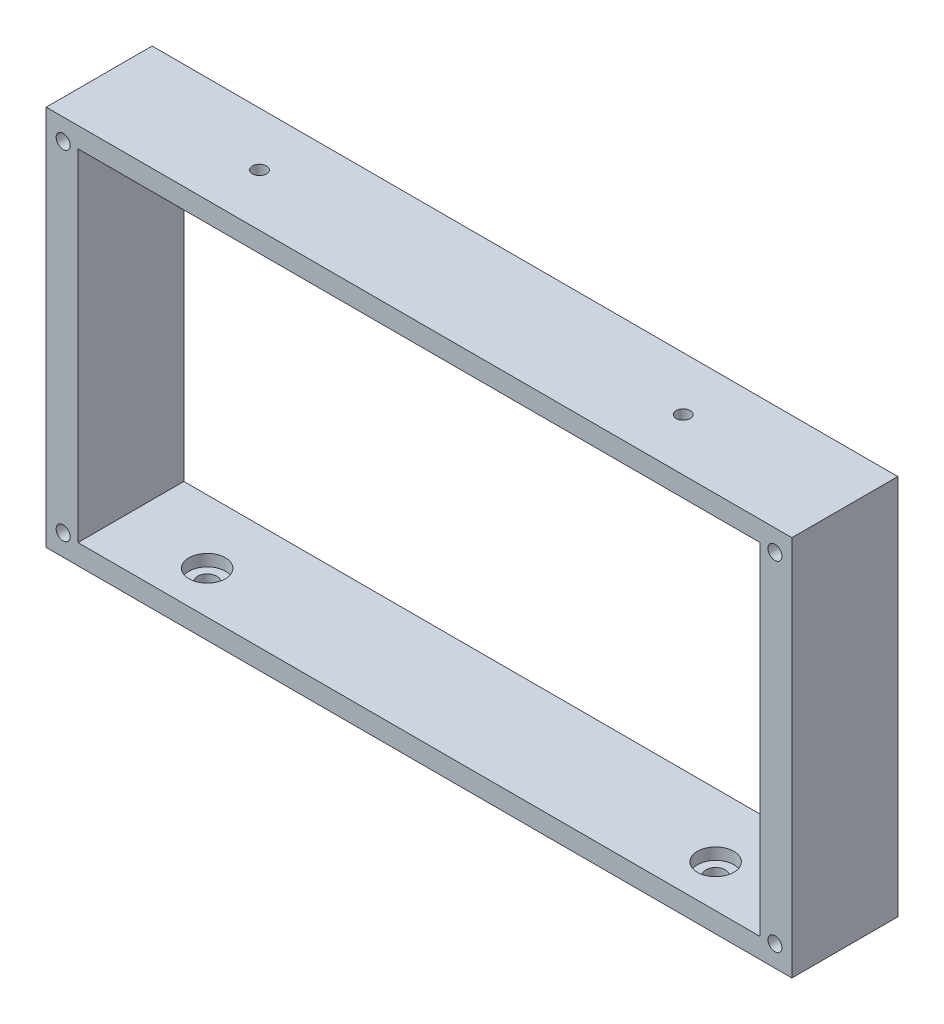
SolidWorks part; units mm, degrees
ref_plane "Front Plane" through (0, 0, 0) normal (0, 0, 1) x (1, 0, 0)
ref_plane "Top Plane" through (0, 0, 0) normal (0, 1, 0) x (1, 0, 0)
ref_plane "Right Plane" through (0, 0, 0) normal (1, 0, 0) x (0, 0, -1)
sketch "Sketch5" plane through (0, 0, 0) normal (0, 0, 1) x (1, 0, 0)
  line L1 (-80.5, -40.25) -> (80.5, -40.25)
  line L2 (-80.5, -40.25) -> (-80.5, 40.25)
  line L3 (-80.5, 40.25) -> (80.5, 40.25)
  line L4 (80.5, -40.25) -> (80.5, 40.25)
  line L5 (-80.5, -40.25) -> (80.5, 40.25) construction
  line L6 (-80.5, 40.25) -> (80.5, -40.25) construction
  line L7 (-88, -45) -> (88, -45)
  line L8 (-88, -45) -> (-88, 45)
  line L9 (-88, 45) -> (88, 45)
  line L10 (88, -45) -> (88, 45)
  line L11 (-88, -45) -> (88, 45) construction
  line L12 (-88, 45) -> (88, -45) construction
  point P0 (0, 0)
  point P6 (0, 0)
  dimension "D1" = 161
  dimension "D2" = 80.5
  dimension "D3" = 176
  dimension "D4" = 90
extrude "Boss-Extrude2" add sketch "Sketch5" along normal blind 25
hole_wizard "M4x0.7 Tapped Hole1" positions "Sketch6" profile "Sketch7" tap size "M4x0.7" standard "ANSI Metric" end condition through all
sketch "Sketch6" plane through (0, 0, 0) normal (0, 0, -1) x (-1, 0, 0)
  line L1 (-84, -40) -> (84, -40)
  line L2 (-84, -40) -> (-84, 40)
  line L3 (-84, 40) -> (84, 40)
  line L4 (84, -40) -> (84, 40)
  line L5 (-84, -40) -> (84, 40) construction
  line L6 (-84, 40) -> (84, -40) construction
  point P1 (0, 0)
  point P2 (84, 40)
  point P115 (-84, -40)
  point P116 (-84, 40)
  point P117 (84, -40)
  dimension "D1" = 168
  dimension "D2" = 80
sketch "Sketch7" plane through (0, 0, 0) normal (1, 0, 0) x (0, 1, 0)
  line L0 (0, 0) -> (0, 25)
  line L1 (0, 25) -> (1.65, 25)
  line L2 (1.65, 25) -> (1.65, 0)
  line L5 (1.65, 0) -> (0, 0)
  line L11 (0, -6.35) -> (0, 107.95) construction
  dimension "Thru Tap Drill Dia." = 3.3
  dimension "Thru Tap Drill Depth" = 25
cosmetic thread "Hole Thread1" parameters "D2"=4
cosmetic thread "Hole Thread2" parameters "D2"=4
cosmetic thread "Hole Thread3" parameters "D2"=4
cosmetic thread "Hole Thread4" parameters "D2"=4
hole_wizard "CBORE for M4 SBHCS1" positions "Sketch8" profile "Sketch10" counterbore size "M4" standard "ANSI Metric" end condition through all
sketch "Sketch8" plane through (0, -40.25, 0) normal (0, 1, 0) x (1, 0, 0)
  line L0 (-60, -15) -> (60, -15)
  line L2 (-88, -25) -> (88, -25) construction
  point P1 (-60, -15)
  point P2 (60, -15)
  point P9 (0, -15)
  dimension "D1" = 120
  dimension "D2" = 10
sketch "Sketch10" plane through (-60, -40.25, 15) normal (1, 0, 0) x (0, 0, 1)
  line L0 (0, 0) -> (0, 4.75)
  line L1 (0, 4.75) -> (2.25, 4.75)
  line L3 (2.25, 4.75) -> (2.25, 2.75)
  line L4 (2.25, 2.75) -> (4.3, 2.75)
  line L5 (4.3, 2.75) -> (4.3, 0)
  line L7 (4.3, 0) -> (0, 0)
  line L11 (0, -6.35) -> (0, 107.95) construction
  dimension "Thru Hole Dia." = 4.5
  dimension "Thru Hole Depth" = 4.75
  dimension "C'Bore Dia." = 8.6
  dimension "C'Bore Depth" = 2.75
hole_wizard "M4x0.7 Tapped Hole2" positions "Sketch11" profile "Sketch12" tap size "M4x0.7" standard "ANSI Metric"
sketch "Sketch11" plane through (0, 0, 0) normal (0, 0, -1) x (-1, 0, 0)
  line L1 (-10, -42.5) -> (10, -42.5)
  line L2 (-10, -42.5) -> (-10, 42.5)
  line L3 (-10, 42.5) -> (10, 42.5)
  line L4 (10, -42.5) -> (10, 42.5)
  line L5 (-10, -42.5) -> (10, 42.5) construction
  line L6 (-10, 42.5) -> (10, -42.5) construction
  line L7 (-88, 45) -> (88, 45) construction
  point P0 (0, 0)
  point P1 (10, 42.5)
  point P48 (-10, -42.5)
  point P49 (-10, 42.5)
  point P50 (10, -42.5)
  dimension "D1" = 20
  dimension "D2" = 2.5
sketch "Sketch12" plane through (0, 0, 0) normal (1, 0, 0) x (0, 1, 0)
  line L0 (0, 0) -> (0, 5.9914)
  line L1 (0, 5.9914) -> (1.65, 5)
  line L2 (1.65, 5) -> (1.65, 0)
  line L5 (1.65, 0) -> (0, 0)
  line L10 (0, 5.9914) -> (-1.65, 5) construction
  line L11 (0, -6.35) -> (0, 107.95) construction
  dimension "Tap Drill Dia." = 3.3
  dimension "Tap Drill Depth" = 5
  dimension "Drill Angle" = 118
cosmetic thread "Hole Thread5" parameters "D1"=25, "D2"=4
cosmetic thread "Hole Thread6" parameters "D1"=25, "D2"=4
cosmetic thread "Hole Thread7" parameters "D1"=25, "D2"=4
cosmetic thread "Hole Thread8" parameters "D1"=25, "D2"=4
hole_wizard "M4x0.7 Tapped Hole3" positions "Sketch13" profile "Sketch14" tap size "M4x0.7" standard "ANSI Metric" end condition up to next
sketch "Sketch13" plane through (0, 45, 0) normal (0, 1, 0) x (1, 0, 0)
  line L0 (-50, -12.6553) -> (50, -12.6553)
  point P1 (-50, -12.6553)
  point P2 (50, -12.6553)
  point P5 (0, -12.6553)
  dimension "D1" = 100
sketch "Sketch14" plane through (-50, 45, 12.6553) normal (1, 0, 0) x (0, 0, 1)
  line L0 (0, 0) -> (0, 4.75)
  line L1 (0, 4.75) -> (1.65, 4.75)
  line L2 (1.65, 4.75) -> (1.65, 0)
  line L5 (1.65, 0) -> (0, 0)
  line L11 (0, -6.35) -> (0, 107.95) construction
  dimension "Thru Tap Drill Dia." = 3.3
  dimension "Thru Tap Drill Depth" = 4.75
cosmetic thread "Hole Thread9" parameters "D2"=4
cosmetic thread "Hole Thread10" parameters "D2"=4
